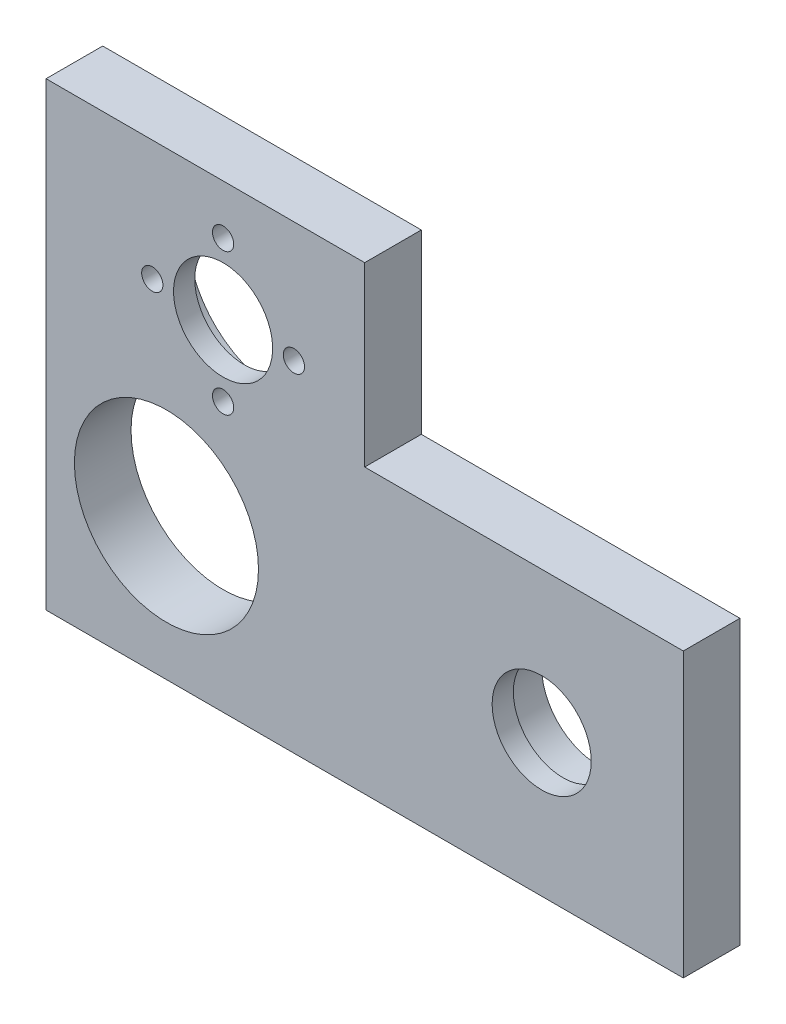
SolidWorks part; units mm, degrees
ref_plane "Front" through (0, 0, 0) normal (0, 0, 1) x (1, 0, 0)
ref_plane "Top" through (0, 0, 0) normal (0, 1, 0) x (1, 0, 0)
ref_plane "Right" through (0, 0, 0) normal (1, 0, 0) x (0, 0, -1)
sketch "Esquisse1" plane through (0, 0, 0) normal (0, 0, 1) x (1, 0, 0)
  line L1 (0, 0) -> (90, 0)
  line L2 (0, 0) -> (0, 65)
  line L3 (0, 65) -> (90, 65)
  line L4 (90, 0) -> (90, 65)
  circle A0 centre (70, 20) radius 7
  circle A1 centre (17, 20) radius 13
  circle A2 centre (25, 48) radius 13
  dimension "D3" = 14
  dimension "D4" = 20
  dimension "D6" = 53
  dimension "D8" = 26
  dimension "D9" = 26
  dimension "D1" = 90
  dimension "D2" = 65
  dimension "D5" = 70
  dimension "D7" = 20
  dimension "D10" = 53
  dimension "D11" = 48
extrude "Boss.-Extru.1" add sketch "Esquisse1" along normal blind 8
sketch "Esquisse2" plane through (0, 0, 0) normal (0, 0, -1) x (-1, 0, 0)
  circle A0 centre (-25, 48) radius 13
  circle A1 centre (-17, 20) radius 13 construction
extrude "Boss.-Extru.2" add sketch "Esquisse2" along normal blind 3 from surface starting at face at (45, 32.5, 8)
sketch "Esquisse3" plane through (0, 0, 5) normal (0, 0, -1) x (-1, 0, 0)
  line L0 (-15, 48) -> (-25, 48) construction
  circle A0 centre (-25, 48) radius 7
  circle A1 centre (-15, 48) radius 1.5
  circle A2 centre (-25, 38) radius 1.5
  circle A3 centre (-35, 48) radius 1.5
  circle A4 centre (-25, 58) radius 1.5
  point P13 (-25, 48)
  dimension "D1" = 14
  dimension "D2" = 3
  dimension "D3" = 10
  dimension "D4" = 4
extrude "Enlèv. mat.-Extru.1" cut sketch "Esquisse3" against normal through all
sketch "Esquisse4" plane through (0, 0, 8) normal (0, 0, 1) x (1, 0, 0)
  circle A0 centre (70, 20) radius 8
  dimension "D1" = 16
extrude "Enlèv. mat.-Extru.2" cut sketch "Esquisse4" along normal blind 5 from surface starting at face at (30, 20, 0)
sketch "Esquisse5" plane through (0, 0, 0) normal (0, 0, -1) x (-1, 0, 0)
  line L1 (-90, 65) -> (-45, 65)
  line L2 (-90, 65) -> (-90, 40)
  line L3 (-90, 40) -> (-45, 40)
  line L4 (-45, 65) -> (-45, 40)
  dimension "D1" = 25
  dimension "D2" = 45
extrude "Enlèv. mat.-Extru.3" cut sketch "Esquisse5" against normal through all
